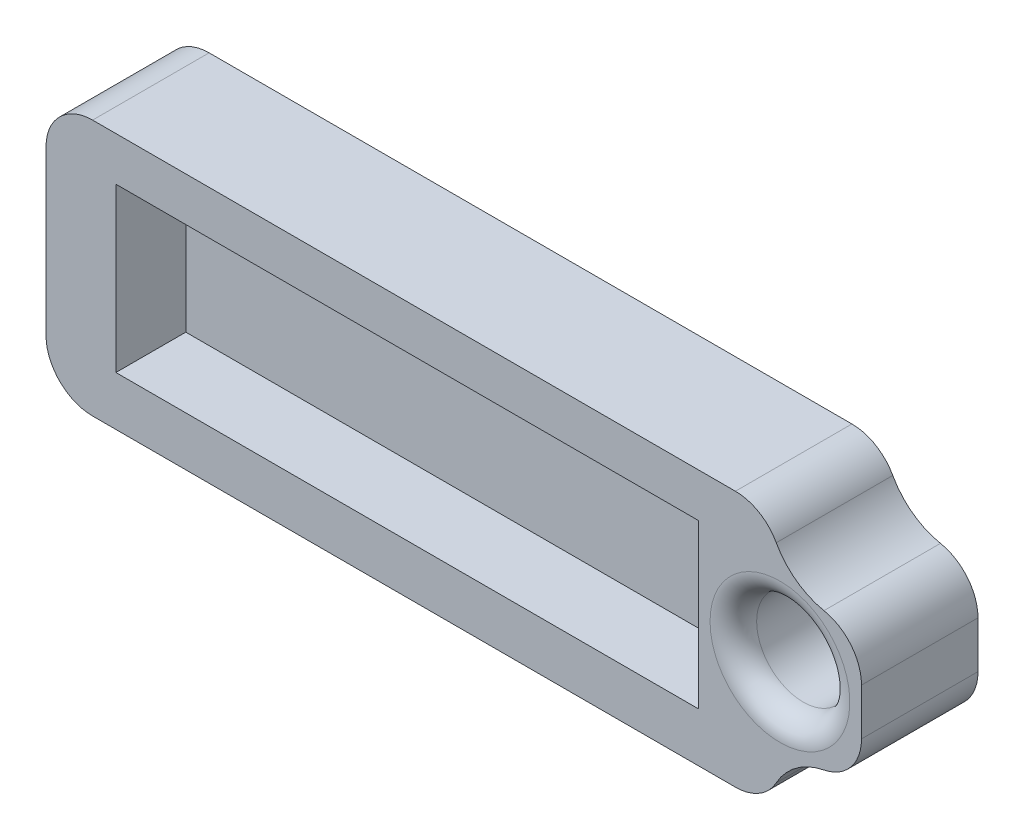
SolidWorks part; units mm, degrees
ref_plane "Front Plane" through (0, 0, 0) normal (0, 0, 1) x (1, 0, 0)
ref_plane "Top Plane" through (0, 0, 0) normal (0, 1, 0) x (1, 0, 0)
ref_plane "Right Plane" through (0, 0, 0) normal (1, 0, 0) x (0, 0, -1)
sketch "Sketch1" plane through (0, 0, 0) normal (0, 1, 0) x (1, 0, 0)
  line L1 (-48.0963, 18.1464) -> (-17.0963, 18.1464)
  line L2 (-48.0963, 18.1464) -> (-48.0963, 13.1464)
  line L3 (-48.0963, 13.1464) -> (-17.0963, 13.1464)
  line L4 (-17.0963, 18.1464) -> (-17.0963, 13.1464)
  dimension "D1" = 31
  dimension "D2" = 5
extrude "Boss-Extrude2" add sketch "Sketch1" along normal blind 11
sketch "Sketch3" plane through (0, 0, -13.1464) normal (0, 0, 1) x (1, 0, 0)
  line L0 (-32.5963, 11) -> (-32.5963, 0.235) construction
  line L1 (-48.0963, 11) -> (-17.0963, 11) construction
  line L3 (-20.0963, 2.1175) -> (-45.0963, 2.1175)
  line L4 (-20.0963, 2.1175) -> (-20.0963, 9.1175)
  line L5 (-20.0963, 9.1175) -> (-45.0963, 9.1175)
  line L6 (-45.0963, 2.1175) -> (-45.0963, 9.1175)
  line L7 (-20.0963, 2.1175) -> (-45.0963, 9.1175) construction
  line L8 (-20.0963, 9.1175) -> (-45.0963, 2.1175) construction
  point P4 (-32.5963, 5.6175)
  dimension "D1" = 25
  dimension "D2" = 7
extrude "Cut-Extrude1" cut sketch "Sketch3" against normal blind 3
sketch "Sketch7" plane through (-17.0963, 0, 0) normal (1, 0, 0) x (0, 0, -1)
  line L0 (15.6464, 11) -> (15.6464, 0) construction
  line L1 (13.1464, 11) -> (18.1464, 11) construction
  line L2 (13.1464, 0) -> (18.1464, 0) construction
  line L3 (13.1464, 11) -> (13.1464, 0) construction
  line L4 (18.1464, 2.5) -> (13.1464, 2.5)
  line L5 (18.1464, 2.5) -> (18.1464, 8.5)
  line L6 (18.1464, 8.5) -> (13.1464, 8.5)
  line L7 (13.1464, 2.5) -> (13.1464, 8.5)
  line L8 (18.1464, 2.5) -> (13.1464, 8.5) construction
  line L9 (18.1464, 8.5) -> (13.1464, 2.5) construction
  point P6 (15.6464, 5.5)
  dimension "D1" = 6
extrude "Boss-Extrude4" add sketch "Sketch7" along normal blind 4
sketch "Sketch8" plane through (0, 0, -13.1464) normal (0, 0, 1) x (1, 0, 0)
  line L0 (-20.0963, 5.6175) -> (-13.0963, 5.6175) construction
  line L1 (-20.0963, 2.1175) -> (-20.0963, 9.1175) construction
  line L2 (-13.0963, 8.5) -> (-13.0963, 2.5) construction
  circle A0 centre (-16.5963, 5.6175) radius 2
extrude "Cut-Extrude2" cut sketch "Sketch8" against normal through all
fillet "Fillet1" radius 1 2 edges at (-14.5963, 5.6175, -18.1464) (-14.5963, 5.6175, -13.1464)
fillet "Fillet3" radius 2 2 edges at (-13.0963, 8.5, -15.6464) (-13.0963, 2.5, -15.6464)
fillet "Fillet4" radius 3 2 edges
fillet "Fillet5" radius 2 4 edges at (-17.0963, 11, -15.6464) (-17.0963, 0, -15.6464) (-48.0963, 0, -15.6464) (-48.0963, 11, -15.6464)
